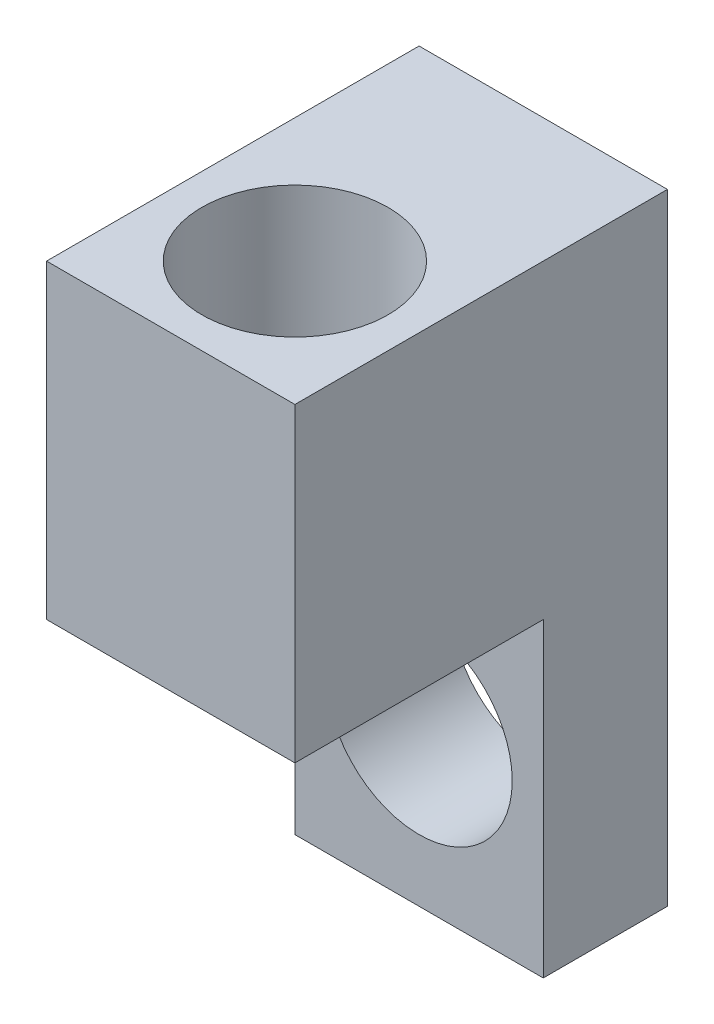
SolidWorks part; units mm, degrees
ref_plane "Plan de face" through (0, 0, 0) normal (0, 0, 1) x (1, 0, 0)
ref_plane "Plan de dessus" through (0, 0, 0) normal (0, 1, 0) x (1, 0, 0)
ref_plane "Plan de droite" through (0, 0, 0) normal (1, 0, 0) x (0, 0, -1)
sketch "Esquisse1" plane through (0, 0, 0) normal (0, 0, 1) x (1, 0, 0)
  line L1 (-4, -10) -> (4, -10)
  line L2 (-4, -10) -> (-4, 10)
  line L3 (-4, 10) -> (4, 10)
  line L4 (4, -10) -> (4, 10)
  line L5 (-4, -10) -> (4, 10) construction
  line L6 (-4, 10) -> (4, -10) construction
  point P0 (0, 0)
  dimension "D1" = 8
  dimension "D2" = 20
extrude "Boss.-Extru.1" add sketch "Esquisse1" along normal blind 12
sketch "Esquisse2" plane through (-4, 0, 0) normal (-1, 0, 0) x (0, 0, 1)
  line L0 (12, 10) -> (0, -10) construction
  line L1 (12, -10) -> (4, -10)
  line L2 (12, -10) -> (12, 0)
  line L3 (12, 0) -> (4, 0)
  line L4 (4, -10) -> (4, 0)
  line L5 (12, -10) -> (0, -10) construction
  line L6 (0, -10) -> (0, 0) construction
  line L7 (0, 10) -> (0, -10) construction
  line L8 (0, 0) -> (4, 0) construction
  dimension "D1" = 4
extrude "Enlèv. mat.-Extru.1" cut sketch "Esquisse2" against normal up to surface (8 mm away) up to face at (4, 0, 6)
sketch "Esquisse3" plane through (0, 0, 0) normal (0, -1, 0) x (1, 0, 0)
  line L0 (-4, 12) -> (4, 4) construction
  line L1 (4, 4) -> (0, 4) construction
  line L2 (4, 4) -> (-4, 4) construction
  line L3 (0, 4) -> (0, 8) construction
  circle A0 centre (0, 8) radius 3
  dimension "D1" = 6
extrude "Enlèv. mat.-Extru.2" cut sketch "Esquisse3" against normal up to surface (10 mm away) up to face at (0, 10, 6)
sketch "Esquisse4" plane through (0, 0, 4) normal (0, 0, 1) x (1, 0, 0)
  line L0 (4, 0) -> (-4, -10) construction
  line L1 (-4, 0) -> (-4, -10) construction
  line L2 (-4, -10) -> (0, -10) construction
  line L3 (4, -10) -> (-4, -10) construction
  line L4 (0, -10) -> (0, -5) construction
  circle A0 centre (0, -5) radius 3
  dimension "D1" = 6
extrude "Enlèv. mat.-Extru.3" cut sketch "Esquisse4" against normal up to surface (4 mm away) up to face at (0, 0, 0)
